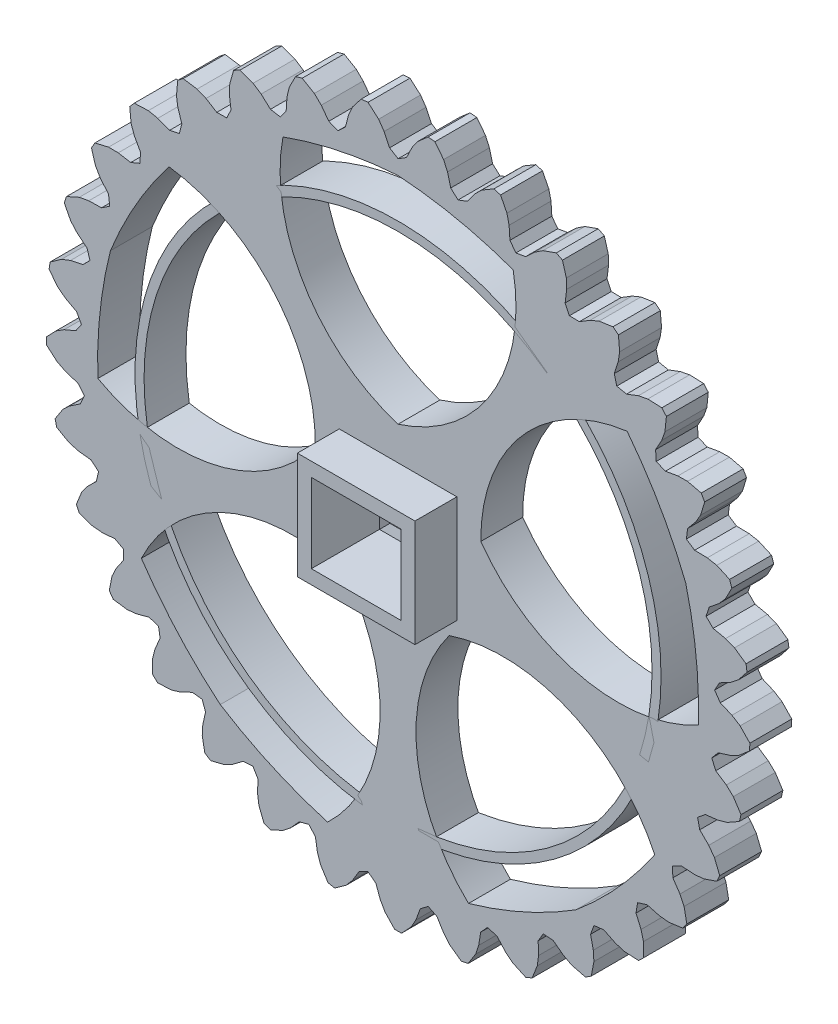
SolidWorks part; units mm, degrees
ref_plane "Front Plane" through (0, 0, 0) normal (0, 0, 1) x (1, 0, 0)
ref_plane "Top Plane" through (0, 0, 0) normal (0, 1, 0) x (1, 0, 0)
ref_plane "Right Plane" through (0, 0, 0) normal (1, 0, 0) x (0, 0, -1)
sketch "Sketch1" plane through (0, 0, 0) normal (0, 0, 1) x (1, 0, 0)
  line L0 (0, 3.775) -> (0, -3.775) construction
  line L1 (4.275, -3.775) -> (-4.275, -3.775)
  line L2 (4.275, -3.775) -> (4.275, 3.775)
  line L3 (4.275, 3.775) -> (-4.275, 3.775)
  line L4 (-4.275, -3.775) -> (-4.275, 3.775)
  line L6 (4.275, 0) -> (-4.275, 0) construction
  circle A0 centre (0, 0) radius 33.6129
  point P3 (0, 3.775)
  point P9 (-4.275, 0)
  dimension "D1" = 67.2257
  dimension "D2" = 8.55
  dimension "D3" = 7.55
extrude "Boss-Extrude1" add sketch "Sketch1" along normal blind 4
sketch "Sketch2" plane through (0, 0, 0) normal (0, 0, 1) x (1, 0, 0)
  line L0 (0, 0) -> (0, 34.8589) construction
  line L1 (0, 30.2608) -> (-0.8069, 30.7591)
  line L2 (-0.8069, 30.7591) -> (-1.33, 31.849)
  line L3 (-1.33, 31.849) -> (-1.8557, 32.6046)
  line L4 (-1.8557, 32.6046) -> (-2.8665, 33.4904)
  line L5 (-2.8665, 33.4904) -> (-1.8557, 34.2629)
  line L6 (-1.8557, 34.2629) -> (0, 34.8589)
  line L7 (1.8557, 34.2629) -> (0, 34.8589)
  line L8 (2.8665, 33.4904) -> (1.8557, 34.2629)
  line L9 (1.8557, 32.6046) -> (2.8665, 33.4904)
  line L10 (1.33, 31.849) -> (1.8557, 32.6046)
  line L11 (0.8069, 30.7591) -> (1.33, 31.849)
  line L12 (0, 30.2608) -> (0.8069, 30.7591)
  circle A22 centre (0, 0) radius 33.6129 construction
  dimension "D5" = 0.5258
  dimension "D6" = 0.7556
  dimension "D9" = 0.5959
  dimension "D1" = 0.8069
  dimension "D2" = 0.4984
  dimension "D3" = 0.5231
  dimension "D4" = 1.0898
  dimension "D7" = 0.8858
  dimension "D8" = 1.8557
  dimension "D10" = 1.0107
  dimension "D11" = 0.7725
  dimension "D12" = 1.0107
extrude "Cut-Extrude1" cut sketch "Sketch2" along normal through all
pattern_circular "CirPattern1" count 33 over 360 about axis through (0, 0, 4) along (0, 0, -1) of "Cut-Extrude1"
sketch "Sketch3" plane through (0, 0, 0) normal (0, 0, 1) x (1, 0, 0)
  circle A0 centre (0, 0) radius 29.75
  dimension "D1" = 59.5
sketch "Sketch4" plane through (0, 0, 0) normal (0, 0, 1) x (1, 0, 0)
  line L0 (0, 0) -> (0, 28.8751) construction
  arc A1 (0, 28.8751) -> (-10.9903, 26.5681) centre (2.6519, -11.0897) ccw
  arc A2 (0, 28.8751) -> (10.9903, 26.5681) centre (-2.6519, -11.0897) cw
  arc A4 (0, 8.31) -> (-10.9903, 26.5681) centre (4.7786, 23.6232) cw
  arc A5 (0, 8.31) -> (10.9903, 26.5681) centre (-4.7786, 23.6232) ccw
extrude "Cut-Extrude2" cut sketch "Sketch4" along normal through all both
sketch "Sketch5" plane through (0, 0, 0) normal (0, 0, 1) x (1, 0, 0)
  circle A0 centre (0, 0) radius 25.1098
  circle A1 centre (0, 0) radius 24.2496
extrude "Boss-Extrude2" add sketch "Sketch5" along normal through all separate body
pattern_circular "CirPattern2" count 5 over 360 about axis through (0, 0, 4) along (0, 0, -1) of "Cut-Extrude2" reverse direction yes
chamfer "Chamfer1" distance 1.5 distance2 0.5 4 edges at (-4.275, 0, 0) (0, -3.775, 0) (4.275, 0, 0) (0, 3.775, 0) first distance on face at (-4.275, 0, 2) first distance on face at (0, -3.775, 2) first distance on face at (4.275, 0, 2) first distance on face at (0, 3.775, 2)
sketch "Sketch6" plane through (0, 0, 4) normal (0, 0, 1) x (1, 0, 0)
  line L1 (-4.275, 3.775) -> (4.275, 3.775)
  line L2 (-4.275, 3.775) -> (-4.275, -3.775)
  line L3 (-4.275, -3.775) -> (4.275, -3.775)
  line L4 (4.275, 3.775) -> (4.275, -3.775)
  line L5 (-5.6131, 5.1131) -> (5.6131, 5.1131)
  line L6 (-5.6131, 5.1131) -> (-5.6131, -5.1131)
  line L7 (-5.6131, -5.1131) -> (5.6131, -5.1131)
  line L8 (5.6131, 5.1131) -> (5.6131, -5.1131)
  dimension "D1" = 1.3381
  dimension "D2" = 1.3381
  dimension "D3" = 1.3381
  dimension "D4" = 1.3381
extrude "Boss-Extrude3" add sketch "Sketch6" along normal blind 4
equation "\"padding\"=1.33807"
equation "\"D1@Sketch6\"=\"padding\""
equation "\"D2@Sketch6\"=\"padding\""
equation "\"D3@Sketch6\"=\"padding\""
equation "\"D4@Sketch6\"=\"padding\""
